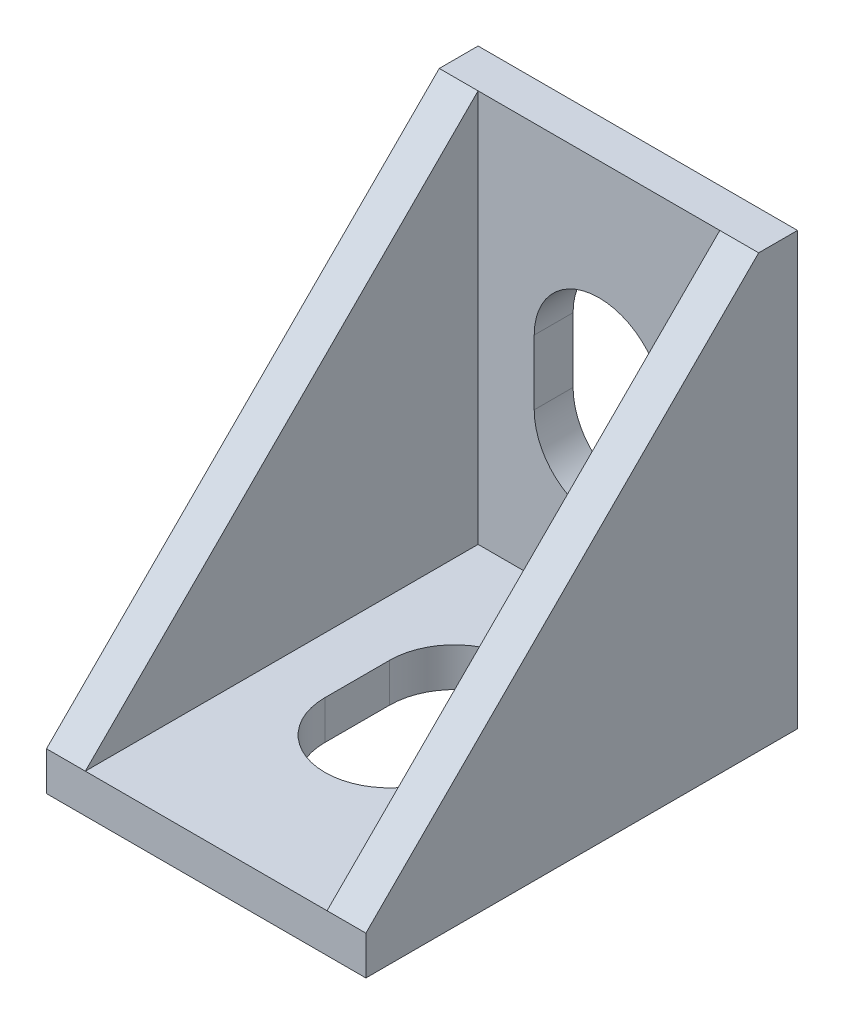
SolidWorks part; units mm, degrees
ref_plane "Front Plane" through (0, 0, 0) normal (0, 0, 1) x (1, 0, 0)
ref_plane "Top Plane" through (0, 0, 0) normal (0, 1, 0) x (1, 0, 0)
ref_plane "Right Plane" through (0, 0, 0) normal (1, 0, 0) x (0, 0, -1)
sketch "Sketch1" plane through (0, 0, 0) normal (0, 1, 0) x (1, 0, 0)
  line L1 (0, 0) -> (14.8, 0)
  line L2 (0, 0) -> (0, -20)
  line L3 (0, -20) -> (14.8, -20)
  line L4 (14.8, 0) -> (14.8, -20)
extrude "Boss-Extrude1" add sketch "Sketch1" along normal blind 1.8 contours L1 L4 L3 L2
sketch "Sketch2" plane through (0, 1.8, 0) normal (0, 1, 0) x (1, 0, 0)
  line L0 (14.8, 0) -> (14.8, -20) construction
  line L1 (0, 0) -> (14.8, 0)
  line L2 (0, 0) -> (0, -1.8)
  line L3 (0, -1.8) -> (14.8, -1.8)
  line L4 (14.8, 0) -> (14.8, -1.8)
extrude "Boss-Extrude2" add sketch "Sketch2" along normal blind 18.2
sketch "Sketch3" plane through (0, 0, 0) normal (0, -1, 0) x (1, 0, 0)
  line L0 (0, 20) -> (14.8, 0) construction
  line L1 (0, 0) -> (14.8, 20) construction
  line L2 (7.4, 11.5) -> (7.4, 8.5) construction
  line L3 (10.4, 11.5) -> (10.4, 8.5)
  line L4 (4.4, 11.5) -> (4.4, 8.5)
  arc A0 (10.4, 11.5) -> (4.4, 11.5) centre (7.4, 11.5) ccw
  arc A1 (4.4, 8.5) -> (10.4, 8.5) centre (7.4, 8.5) ccw
  point P10 (7.4, 10)
extrude "Cut-Extrude2" cut sketch "Sketch3" against normal through all
sketch "Sketch5" plane through (0, 0, 0) normal (0, 0, -1) x (-1, 0, 0)
  line L0 (-14.8, 20) -> (0, 0) construction
  line L1 (-14.8, 0) -> (0, 20) construction
  line L2 (-7.4, 11.5) -> (-7.4, 8.5) construction
  line L3 (-4.4, 11.5) -> (-4.4, 8.5)
  line L4 (-10.4, 11.5) -> (-10.4, 8.5)
  arc A0 (-4.4, 11.5) -> (-10.4, 11.5) centre (-7.4, 11.5) ccw
  arc A1 (-10.4, 8.5) -> (-4.4, 8.5) centre (-7.4, 8.5) ccw
  point P10 (-7.4, 10)
extrude "Cut-Extrude3" cut sketch "Sketch5" against normal blind 17.2
sketch "Sketch6" plane through (0, 0, 0) normal (-1, 0, 0) x (0, 0, 1)
  line L0 (1.8, 20) -> (1.8, 1.8)
  line L1 (1.8, 1.8) -> (20, 1.8)
  line L2 (20, 1.8) -> (1.8, 20)
extrude "Boss-Extrude3" add sketch "Sketch6" against normal blind 1.8
sketch "Sketch7" plane through (14.8, 0, 0) normal (1, 0, 0) x (0, 0, -1)
  line L0 (-1.8, 20) -> (-1.8, 1.8)
  line L1 (-1.8, 1.8) -> (-20, 1.8)
  line L2 (-20, 1.8) -> (-1.8, 20)
extrude "Boss-Extrude4" add sketch "Sketch7" against normal blind 1.8
move or copy body "Body-Move/Copy1" [suppressed] bodies to move or copy 106
